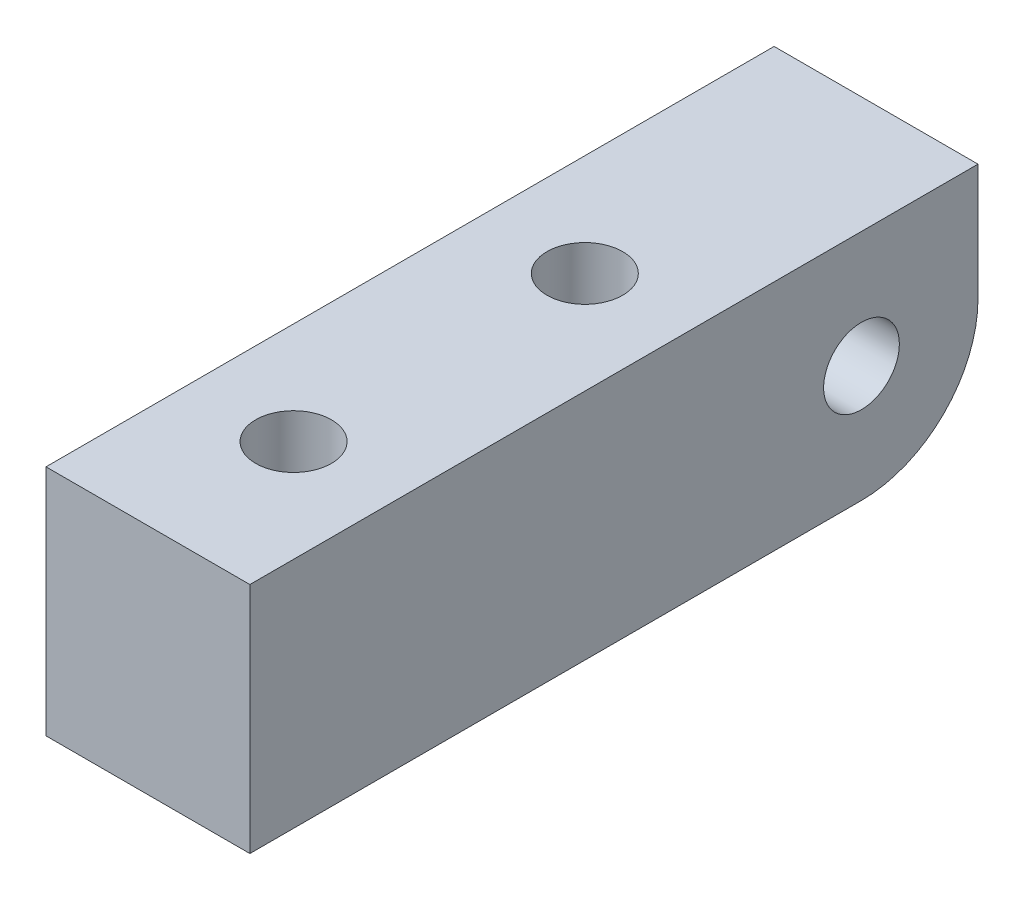
SolidWorks part; units mm, degrees
ref_plane "Front Plane" through (0, 0, 0) normal (0, 0, 1) x (1, 0, 0)
ref_plane "Top Plane" through (0, 0, 0) normal (0, 1, 0) x (1, 0, 0)
ref_plane "Right Plane" through (0, 0, 0) normal (1, 0, 0) x (0, 0, -1)
sketch "Sketch1" plane through (0, 0, 0) normal (1, 0, 0) x (0, 0, -1)
  line L0 (-4, 4) -> (-4, -4) construction
  line L1 (4, 4) -> (-21, 4)
  line L2 (4, 4) -> (4, -4)
  line L3 (4, -4) -> (-21, -4)
  line L4 (-21, 4) -> (-21, -4)
  line L5 (-7.3, 4) -> (-4.7, 4)
  line L6 (-7.3, 4) -> (-7.3, -4)
  line L7 (-7.3, -4) -> (-4.7, -4)
  line L8 (-4.7, 4) -> (-4.7, -4)
  line L9 (-4.7, 0) -> (-7.3, 0) construction
  line L11 (-6, 1.3) -> (-6, -1.5166) construction
  circle A0 centre (0, 0) radius 1.3
  circle A1 centre (0, 0) radius 4
  dimension "D1" = 2.6
  dimension "D2" = 8
  dimension "D3" = 2.6
  dimension "D4" = 10
  dimension "D5" = 25
  dimension "D6" = 1.3
extrude "Boss-Extrude1" add sketch "Sketch1" along normal mid plane 7 contours A1 A0 | A1 L2 L1 | L1 L0 A1 | L0 L1 L8 L3 | L8 L1 L6 L3 | L6 L1 L4 L3 | A1 L0 L3 region at (0, 0, 6) region at (0, 3.9072, 2.35) region at (0, 0, 14.15) region at (0, 3.1065, -3.1065) region at (0, 2.7484, -2.7484) region at (0, -3.1065, -3.1065)
sketch "Sketch3" plane through (0, 4, 0) normal (0, 1, 0) x (1, 0, 0)
  line L4 (3.5, 4) -> (-3.5, 4) construction
  circle A0 centre (0, -6) radius 1.3
  circle A3 centre (0, -16) radius 1.3
  dimension "D1" = 2.6
  dimension "D2" = 10
  dimension "D3" = 10
fillet "Fillet1" radius 4 1 edges at (0, -4, -4)
extrude "Cut-Extrude6" cut sketch "Sketch3" against normal through all
sketch "Sketch5" plane through (0, -4, 0) normal (0, -1, 0) x (1, 0, 0)
  circle A0 centre (0, 16) radius 2.5
  circle A1 centre (0, 6) radius 2.5
  dimension "D1" = 5
extrude "Cut-Extrude7" cut sketch "Sketch5" against normal blind 3
